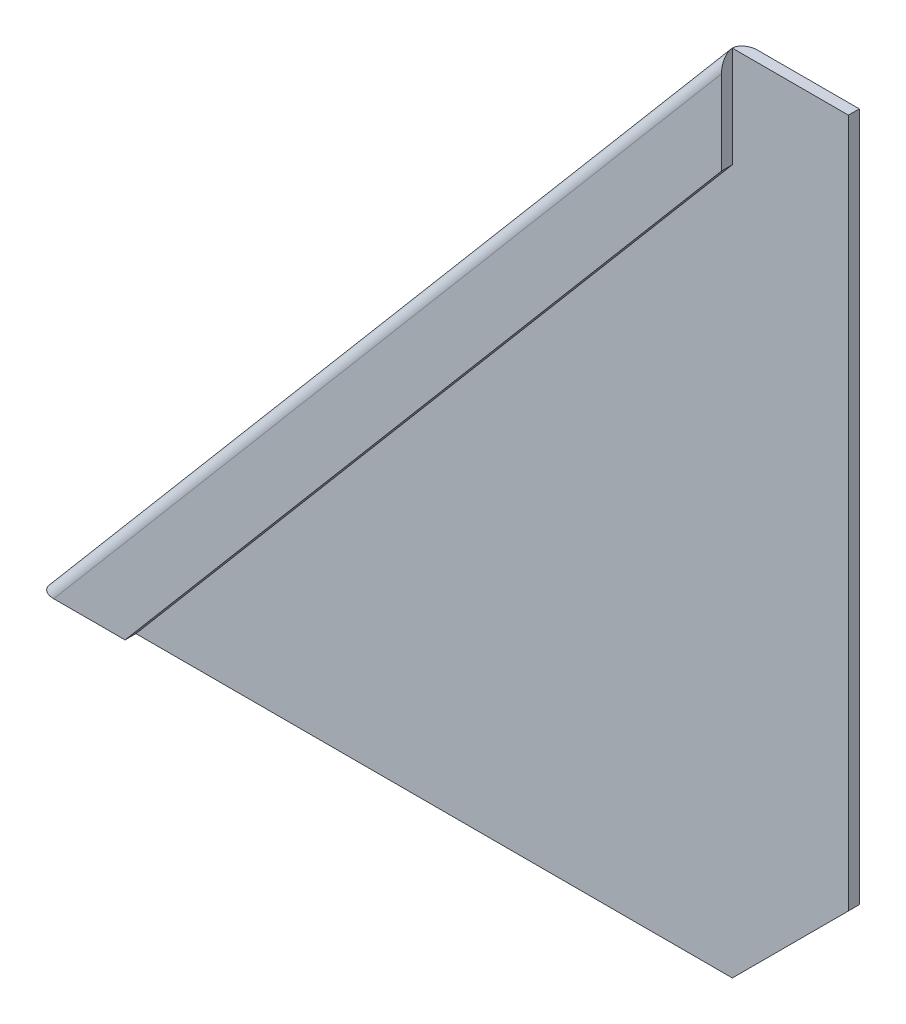
SolidWorks part; units mm, degrees
ref_plane "前基準面" through (0, 0, 0) normal (0, 0, 1) x (1, 0, 0)
ref_plane "上基準面" through (0, 0, 0) normal (0, 1, 0) x (1, 0, 0)
ref_plane "右基準面" through (0, 0, 0) normal (1, 0, 0) x (0, 0, -1)
ref_plane "平面1"
sketch "草圖1" plane through (0, 0, 0) normal (0, 0, 1) x (1, 0, 0)
  line L0 (-16, 0) -> (0, 16)
  line L1 (0, 16) -> (0, 111)
  line L2 (0, 111) -> (-16, 111)
  line L3 (-16, 111) -> (-16, 97.0735)
  line L4 (-16, 97.0735) -> (-98.2064, 0)
  line L5 (-98.2064, 0) -> (-16, 0)
  dimension "D1" = 16
  dimension "D2" = 16
  dimension "D3" = 95
  dimension "D4" = 16
extrude "擠出1" add sketch "草圖1" along normal blind 1.5
ref_plane "平面2"
sketch "草圖2" plane through (0, 0, 0) normal (0, 0, 1) x (1, 0, 0)
  line L0 (-110, 0) -> (-98.2064, 0)
  line L1 (-98.2064, 0) -> (-16, 97.0735)
  line L2 (-16, 97.0735) -> (-16, 111)
  line L3 (-16, 111) -> (-110, 0)
extrude "擠出2" add sketch "草圖2" along normal blind 3
fillet "圓角1" radius 1.5 2 edges at (-63, 55.5, 0) (-63, 55.5, 3)
